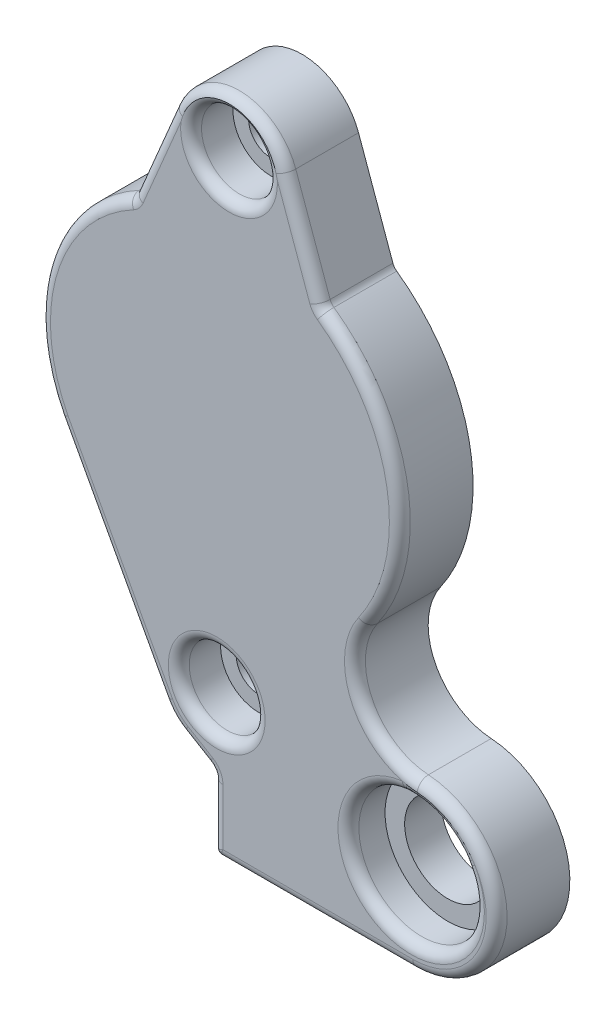
SolidWorks part; units mm, degrees
ref_plane "Front Plane" through (0, 0, 0) normal (0, 0, 1) x (1, 0, 0)
ref_plane "Top Plane" through (0, 0, 0) normal (0, 1, 0) x (1, 0, 0)
ref_plane "Right Plane" through (0, 0, 0) normal (1, 0, 0) x (0, 0, -1)
sketch "Sketch1" plane through (0, 0, 0) normal (0, 0, 1) x (1, 0, 0)
  line L0 (91.5, 310) -> (457.5, 310) construction
  line L1 (114.8081, 402.0649) -> (475.255, 389.4778) construction
sketch "Sketch4" plane through (0, 0, 0) normal (0, 0, 1) x (1, 0, 0)
  line L0 (56.1428, 46.5222) -> (74.7914, 46.5222)
  line L1 (55.6428, 52.9164) -> (55.6428, 47.0222)
  line L4 (40.956, 75.5605) -> (50.9514, 57.1049)
  line L5 (55.1562, 53.7746) -> (52.7813, 55.1952)
  line L6 (57.224, 105.2234) -> (56.0511, 60.2234) construction
  line L7 (48.0858, 97.6068) -> (51.9146, 106.6569)
  line L8 (65.8961, 97.2047) -> (62.6086, 106.3601)
  arc A0 (74.7914, 46.5222) -> (75.2897, 62.5474) centre (74.7914, 54.5425) ccw
  arc A5 (50.9514, 57.1049) -> (52.7813, 55.1952) centre (55.348, 59.4861) ccw
  arc A6 (56.1428, 46.5222) -> (55.6428, 47.0222) centre (56.1428, 47.0222) cw
  circle A7 centre (57.224, 105.2234) radius 2.125
  circle A8 centre (56.0511, 60.2234) radius 2.125
  circle A9 centre (74.6428, 54.833) radius 4.125
  arc A10 (55.6428, 52.9164) -> (55.1562, 53.7746) centre (54.6428, 52.9164) ccw
  arc A11 (75.2897, 62.5474) -> (70.425, 72.6413) centre (75.6887, 68.9589) cw
  arc A12 (70.425, 72.6413) -> (66.2581, 96.7274) centre (56.2106, 82.5857) ccw
  arc A13 (40.956, 75.5605) -> (47.6372, 97.1151) centre (55.2299, 82.9488) cw
  arc A14 (51.9146, 106.6569) -> (62.6086, 106.3601) centre (57.2036, 104.4193) cw
  arc A15 (66.2581, 96.7274) -> (65.8961, 97.2047) centre (66.8372, 97.5426) cw
  arc A16 (47.6372, 97.1151) -> (48.0858, 97.6068) centre (47.1648, 97.9964) ccw
  dimension "D1" = 5
  dimension "D2" = 0.5
  dimension "D3" = 4.25
  dimension "D4" = 4.25
  dimension "D5" = 8.25
  dimension "D6" = 1
  dimension "D8" = 1
  dimension "D7" = 45
  dimension "D9" = 19
extrude "Boss-Extrude2" add sketch "Sketch4" along normal blind 7
fillet "Fillet1" radius 1 19 edges at (78.7678, 54.833, 7) (59.349, 105.2234, 7) (65.4671, 46.5222, 7) (55.7893, 46.6687, 7) (55.6428, 49.9693, 7) (55.5127, 53.4097, 7) (53.9687, 54.4849, 7) (51.7378, 56.0269, 7) (45.9537, 66.3327, 7) (39.8778, 87.7075, 7) (47.9036, 97.3225, 7) (50.0002, 102.1319, 7) (57.363, 110.1599, 7) (64.2524, 101.7824, 7) (66.0405, 96.9383, 7) (73.3043, 85.543, 7) (69.9018, 66.17, 7) (82.8078, 54.2933, 7) (58.1761, 60.2234, 7)
sketch "Sketch5" plane through (0, 0, 7) normal (0, 0, 1) x (1, 0, 0)
  circle A0 centre (56.0511, 60.2234) radius 2.125 construction
  circle A1 centre (57.224, 105.2234) radius 2.125 construction
  circle A2 centre (57.224, 105.2234) radius 3.625
  circle A3 centre (56.0511, 60.2234) radius 3.625
  circle A6 centre (56.0511, 60.2234) radius 2.125
  circle A7 centre (57.224, 105.2234) radius 2.125
  dimension "D1" = 7.25
  dimension "D2" = 7.25
extrude "Cut-Extrude1" cut sketch "Sketch5" against normal blind 4 contours A3 | A2
fillet "Fillet2" radius 1 2 edges at (59.6761, 60.2234, 7) (60.849, 105.2234, 7)
sketch "Sketch6" plane through (0, 0, 7) normal (0, 0, 1) x (1, 0, 0)
  circle A0 centre (74.6428, 54.833) radius 4.125 construction
  circle A1 centre (74.6428, 54.833) radius 4.125
  circle A2 centre (74.6428, 54.833) radius 6
  dimension "D1" = 12
extrude "Cut-Extrude2" cut sketch "Sketch6" against normal blind 3.5 contours A2
fillet "Fillet3" radius 1 1 edges at (80.6428, 54.833, 7)
